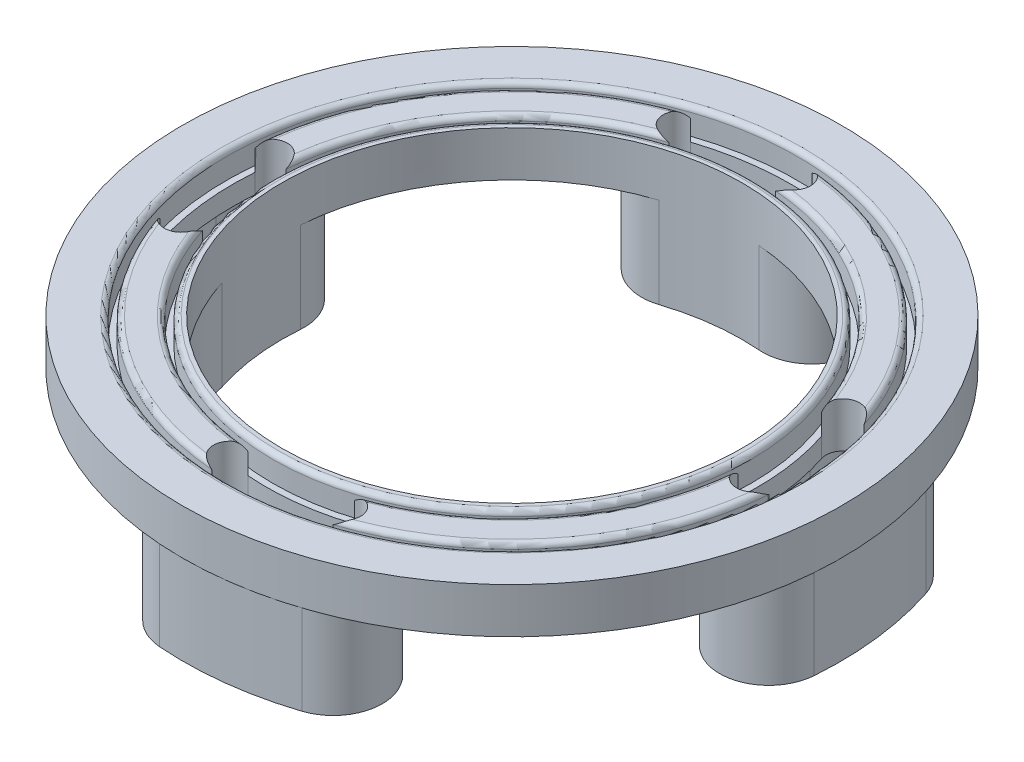
SolidWorks part; units mm, degrees
ref_plane "前视基准面" through (0, 0, 0) normal (0, 0, 1) x (1, 0, 0)
ref_plane "上视基准面" through (0, 0, 0) normal (0, 1, 0) x (1, 0, 0)
ref_plane "右视基准面" through (0, 0, 0) normal (1, 0, 0) x (0, 0, -1)
other "Configuration Table"
sketch "草图1" plane through (0, 0, 0) normal (0, 1, 0) x (1, 0, 0)
  circle A0 centre (0, 0) radius 25.5
extrude "凸台-拉伸1" add sketch "草图1" along normal blind 3.5
sketch "草图2" plane through (0, 3.5, 0) normal (0, 1, 0) x (1, 0, 0)
  circle A0 centre (0, 0) radius 19
  circle A1 centre (0, 0) radius 18.5
  dimension "D1" = 0.5
  dimension "D2" = 37
extrude "切除-拉伸1" cut sketch "草图2" against normal blind 2
sketch "草图3" plane through (0, 3.5, 0) normal (0, 1, 0) x (1, 0, 0)
  circle A0 centre (0, 0) radius 22.1
  circle A1 centre (0, 0) radius 21.6
  dimension "D1" = 0.5
  dimension "D2" = 43.2
extrude "切除-拉伸2" cut sketch "草图3" against normal blind 2
fillet "圆角1" radius 0.4 4 edges at (0, 3.5, 18.5) (0, 3.5, 19) (0, 3.5, 21.6) (0, 3.5, 22.1)
sketch "草图4" plane through (0, 0, 0) normal (0, -1, 0) x (1, 0, 0)
  circle A0 centre (0, 0) radius 19 construction
  circle A1 centre (0, 0) radius 21.6 construction
  arc A2 (-18.0617, 5.8972) -> (-18.9435, -1.4636) centre (0, 0) ccw
  arc A3 (-20.5333, 6.7041) -> (-21.5358, -1.6639) centre (0, 0) ccw
  arc A4 (-21.5358, -1.6639) -> (-18.9435, -1.4636) centre (-20.2397, -1.5638) ccw
  arc A5 (-18.0617, 5.8972) -> (-20.5333, 6.7041) centre (-19.2975, 6.3007) ccw
  arc A8 (-1.6639, 21.5358) -> (-1.4636, 18.9435) centre (-1.5638, 20.2397) ccw
  arc A9 (5.8972, 18.0617) -> (6.7041, 20.5333) centre (6.3007, 19.2975) ccw
  arc A12 (21.5358, 1.6639) -> (18.9435, 1.4636) centre (20.2397, 1.5638) ccw
  arc A13 (18.0617, -5.8972) -> (20.5333, -6.7041) centre (19.2975, -6.3007) ccw
  arc A16 (1.6639, -21.5358) -> (1.4636, -18.9435) centre (1.5638, -20.2397) ccw
  arc A17 (-5.8972, -18.0617) -> (-6.7041, -20.5333) centre (-6.3007, -19.2975) ccw
  arc A22 (-5.8972, -18.0617) -> (1.4636, -18.9435) centre (0, 0) ccw
  arc A23 (-6.7041, -20.5333) -> (1.6639, -21.5358) centre (0, 0) ccw
  arc A26 (18.0617, -5.8972) -> (18.9435, 1.4636) centre (0, 0) ccw
  arc A27 (20.5333, -6.7041) -> (21.5358, 1.6639) centre (0, 0) ccw
  arc A30 (5.8972, 18.0617) -> (-1.4636, 18.9435) centre (0, 0) ccw
  arc A31 (6.7041, 20.5333) -> (-1.6639, 21.5358) centre (0, 0) ccw
  circle A34 centre (-13.2059, -15.4174) radius 1.3 [skipped]
  circle A35 centre (-18.1006, -9.1901) radius 1.3 [skipped]
  circle A36 centre (15.4174, -13.2059) radius 1.3 [skipped]
  circle A37 centre (9.1901, -18.1006) radius 1.3 [skipped]
  circle A38 centre (13.2059, 15.4174) radius 1.3 [skipped]
  circle A39 centre (18.1006, 9.1901) radius 1.3 [skipped]
  circle A40 centre (-15.4174, 13.2059) radius 1.3 [skipped]
  circle A41 centre (-9.1901, 18.1006) radius 1.3 [skipped]
  point P40 (0, 0)
  dimension "D1" = 16
extrude "切除-拉伸5" cut sketch "草图4" against normal through all
sketch "草图5" plane through (0, 0, 0) normal (0, -1, 0) x (1, 0, 0)
  arc A0 (5.5247, 16.9209) -> (7.8836, 24.1456) centre (6.7041, 20.5333) ccw
  arc A1 (7.8836, 24.1456) -> (-1.9566, 25.3245) centre (0, 0) ccw
  arc A2 (-1.9566, 25.3245) -> (-1.3712, 17.7471) centre (-1.6639, 21.5358) ccw
  arc A3 (5.5247, 16.9209) -> (-1.3712, 17.7471) centre (0, 0) ccw
  arc A4 (-17.3962, 5.6799) -> (-18.2456, -1.4097) centre (0, 0) ccw
  arc A5 (-24.826, -1.9181) -> (-18.2456, -1.4097) centre (-21.5358, -1.6639) ccw
  arc A6 (-23.6703, 7.7284) -> (-24.826, -1.9181) centre (0, 0) ccw
  arc A7 (-17.3962, 5.6799) -> (-23.6703, 7.7284) centre (-20.5333, 6.7041) ccw
  arc A12 (5.6799, 17.3962) -> (7.7284, 23.6703) centre (6.7041, 20.5333) ccw
  arc A13 (7.7284, 23.6703) -> (-1.9181, 24.826) centre (0, 0) ccw
  arc A14 (-1.9181, 24.826) -> (-1.4097, 18.2456) centre (-1.6639, 21.5358) ccw
  arc A15 (5.6799, 17.3962) -> (-1.4097, 18.2456) centre (0, 0) ccw
  arc A20 (17.3962, -5.6799) -> (23.6703, -7.7284) centre (20.5333, -6.7041) ccw
  arc A21 (23.6703, -7.7284) -> (24.826, 1.9181) centre (0, 0) ccw
  arc A22 (24.826, 1.9181) -> (18.2456, 1.4097) centre (21.5358, 1.6639) ccw
  arc A23 (17.3962, -5.6799) -> (18.2456, 1.4097) centre (0, 0) ccw
  arc A28 (-5.6799, -17.3962) -> (1.4097, -18.2456) centre (0, 0) ccw
  arc A29 (1.9181, -24.826) -> (1.4097, -18.2456) centre (1.6639, -21.5358) ccw
  arc A30 (-7.7284, -23.6703) -> (1.9181, -24.826) centre (0, 0) ccw
  arc A31 (-5.6799, -17.3962) -> (-7.7284, -23.6703) centre (-6.7041, -20.5333) ccw
  arc A36 (16.9209, -5.5247) -> (24.1456, -7.8836) centre (20.5333, -6.7041) ccw
  arc A37 (24.1456, -7.8836) -> (25.3245, 1.9566) centre (0, 0) ccw
  arc A38 (25.3245, 1.9566) -> (17.7471, 1.3712) centre (21.5358, 1.6639) ccw
  arc A39 (16.9209, -5.5247) -> (17.7471, 1.3712) centre (0, 0) ccw
  arc A40 (-5.5247, -16.9209) -> (-7.8836, -24.1456) centre (-6.7041, -20.5333) ccw
  arc A41 (-7.8836, -24.1456) -> (1.9566, -25.3245) centre (0, 0) ccw
  arc A42 (1.9566, -25.3245) -> (1.3712, -17.7471) centre (1.6639, -21.5358) ccw
  arc A43 (-5.5247, -16.9209) -> (1.3712, -17.7471) centre (0, 0) ccw
  arc A44 (-16.9209, 5.5247) -> (-17.7471, -1.3712) centre (0, 0) ccw
  arc A45 (-25.3245, -1.9566) -> (-17.7471, -1.3712) centre (-21.5358, -1.6639) ccw
  arc A46 (-24.1456, 7.8836) -> (-25.3245, -1.9566) centre (0, 0) ccw
  arc A47 (-16.9209, 5.5247) -> (-24.1456, 7.8836) centre (-20.5333, 6.7041) ccw
  dimension "D1" = 0.5
extrude "凸台-拉伸2" add sketch "草图5" along normal blind 7
sketch "草图7" plane through (0, 3.5, 0) normal (0, 1, 0) x (1, 0, 0)
  circle A0 centre (0, 0) radius 17.8
extrude "切除-拉伸7" cut sketch "草图7" against normal blind 10
